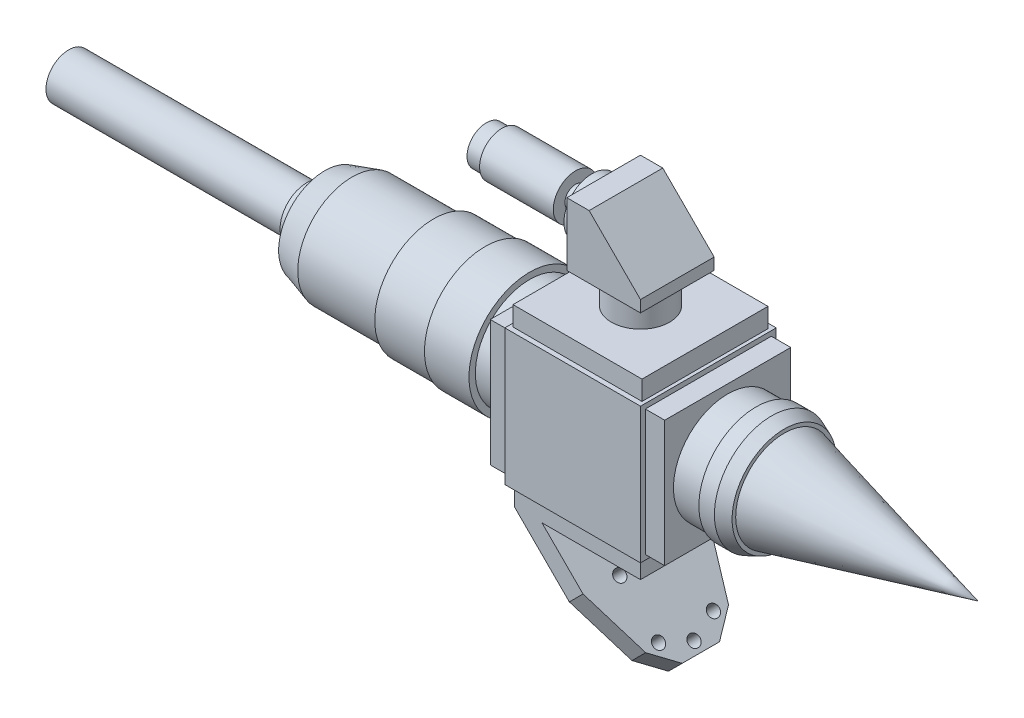
SolidWorks part; units mm, degrees
ref_plane "Front Plane" through (0, 0, 0) normal (0, 0, 1) x (1, 0, 0)
ref_plane "Top Plane" through (0, 0, 0) normal (0, 1, 0) x (1, 0, 0)
ref_plane "Right Plane" through (0, 0, 0) normal (1, 0, 0) x (0, 0, -1)
sketch "Sketch1" plane through (0, 0, 0) normal (0, 0, 1) x (1, 0, 0)
  line L1 (-35, 35) -> (35, 35) construction
  line L2 (-35, 35) -> (-35, -35) construction
  line L3 (-35, -35) -> (35, -35) construction
  line L4 (35, 35) -> (35, -35) construction
  dimension "D1" = 70
  dimension "D2" = 70
  dimension "D3" = 35
  dimension "D4" = 35
sketch "Sketch2" plane through (0, 0, 0) normal (0, 0, 1) x (1, 0, 0)
  line L0 (0, 0) -> (151.8037, 1.6334) construction
  line L1 (0, 0) -> (-331.3481, 0) construction
  line L3 (-35, 35) -> (35, 35)
  line L4 (-35, 35) -> (-35, -35)
  line L5 (-35, -35) -> (35, -35)
  line L6 (35, 35) -> (35, -35)
extrude "Boss-Extrude1" add sketch "Sketch2" along normal blind 35 and the other way blind 35
sketch "Sketch3" plane through (0, 0, 0) normal (0, 0, 1) x (1, 0, 0)
  line L0 (123.9014, 0) -> (-533.4709, 0) construction
  line L1 (35, 35) -> (35, -35) construction
  line L2 (35, -32.5) -> (45, -32.5)
  line L3 (35, -32.5) -> (35, 32.5)
  line L4 (-123.9014, 0) -> (533.4709, 0) construction
  line L5 (45, -32.5) -> (45, 32.5)
  line L6 (35, 32.5) -> (45, 32.5)
  line L7 (0, 0.6089) -> (0, 46.7598) construction
  dimension "D1" = 32.5
  dimension "D2" = 10
extrude "Boss-Extrude2" add sketch "Sketch3" along normal blind 32.5 and the other way blind 32.5
sketch "Sketch20" plane through (0, 0, 0) normal (0, 0, 1) x (1, 0, 0)
  line L0 (-35, 35) -> (-35, -35) construction
  line L1 (-35, 32.5) -> (-45, 32.5)
  line L2 (-35, 32.5) -> (-35, -32.5)
  line L3 (-35, -32.5) -> (-45, -32.5)
  line L4 (-45, 32.5) -> (-45, -32.5)
  line L5 (0, 0) -> (-92.839, 0) construction
  dimension "D1" = 10
  dimension "D2" = 32.5
  dimension "D3" = 65
extrude "Boss-Extrude10" add sketch "Sketch20" along normal blind 32.5 and the other way blind 32.5
sketch "Sketch4" plane through (0, 0, 0) normal (0, 0, 1) x (1, 0, 0)
  line L0 (126.079, 0) -> (-324.8833, 0) construction
  line L1 (45, 28) -> (59.608, 28)
  line L2 (45, -32.5) -> (45, 32.5) construction
  line L3 (59.608, 28) -> (59.608, 29.5)
  line L4 (59.608, 29.5) -> (67.608, 29.5)
  line L5 (67.608, 29.5) -> (74.108, 26.857)
  line L6 (74.108, 26.857) -> (74.108, 0)
  line L7 (45, 28) -> (45, 0)
  line L24 (74.108, 0) -> (45, 0)
  dimension "D1" = 28
  dimension "D2" = 1.5
  dimension "D3" = 8
  dimension "D4" = 6.5
revolve "Revolve1" add sketch "Sketch4" angle 360 about L0
sketch "Sketch5" plane through (0, 0, 0) normal (0, 0, 1) x (1, 0, 0)
  line L0 (0, 0) -> (243.065, 0) construction
  line L1 (74.108, 25) -> (174.108, 0)
  line L2 (74.108, -26.857) -> (74.108, 26.857) construction
  line L3 (174.108, 0) -> (74.108, 0)
  line L4 (74.108, 0) -> (74.108, 25)
  dimension "D1" = 100
  dimension "D2" = 25
revolve "Revolve2" add sketch "Sketch5" angle 360 about L0
sketch "Sketch11" plane through (0, 0, 0) normal (0, 0, 1) x (1, 0, 0)
  line L0 (0, 0) -> (-327.6417, 0) construction
  line L1 (-45, 28) -> (-57.2011, 28)
  line L2 (-57.2011, 28) -> (-57.2011, 31.2886)
  line L3 (-57.2011, 31.2886) -> (-80.1478, 31.2886)
  line L4 (-80.1478, 31.2886) -> (-80.1478, 30.3397)
  line L5 (-80.1478, 30.3397) -> (-106.7356, 30.3397)
  line L6 (-106.7356, 30.3397) -> (-106.7356, 28)
  line L7 (-106.7356, 28) -> (-148.8045, 28)
  line L8 (-148.8045, 28) -> (-162.9019, 23.7683)
  line L9 (-162.9019, 23.7683) -> (-162.9019, 13.7518)
  line L10 (-162.9019, 13.7518) -> (-172.1765, 13.7518)
  line L11 (-172.1765, 13.7518) -> (-172.1765, 11.7113)
  line L12 (-172.1765, 11.7113) -> (-294.986, 11.7113)
  line L13 (-294.986, 11.7113) -> (-294.986, 0)
  line L14 (-45, 28) -> (-45, 0)
  line L15 (-294.986, 0) -> (-45, 0)
revolve "Revolve4" add sketch "Sketch11" angle 360 about L0
sketch "Sketch10" [suppressed] plane through (0, 0, 0) normal (0, 0, 1) x (1, 0, 0)
  line L0 (0, 0) -> (0, 255.2777) construction
  line L1 (28, 35) -> (28, 47.2011)
  line L2 (28, 47.2011) -> (31.2886, 47.2011)
  line L3 (31.2886, 47.2011) -> (31.2886, 70.1478)
  line L4 (31.2886, 70.1478) -> (30.3397, 70.1478)
  line L5 (30.3397, 70.1478) -> (30.3397, 96.7356)
  line L6 (30.3397, 96.7356) -> (28, 96.7356)
  line L7 (28, 96.7356) -> (28, 138.8045)
  line L8 (28, 138.8045) -> (23.7683, 152.9019)
  line L9 (23.7683, 152.9019) -> (13.7518, 152.9019)
  line L10 (13.7518, 152.9019) -> (13.7518, 162.1765)
  line L11 (13.7518, 162.1765) -> (11.7113, 162.1765)
  line L12 (11.7113, 162.1765) -> (11.7113, 284.986)
  line L13 (11.7113, 284.986) -> (0, 284.986)
  line L14 (28, 35) -> (0, 35)
  line L15 (0, 284.986) -> (0, 35)
revolve "Revolve3" [suppressed] add sketch "Sketch10" angle 360 about L0
sketch "Sketch6" plane through (0, -35, 0) normal (0, -1, 0) x (1, 0, 0)
  line L12 (32.5, -32.5) -> (32.5, 32.5)
  line L13 (32.5, 32.5) -> (-32.5, 32.5)
  line L14 (-32.5, 32.5) -> (-32.5, -32.5)
  line L15 (-32.5, -32.5) -> (32.5, -32.5)
  line L16 (32.5, -32.5) -> (32.5, 32.5)
  line L17 (32.5, 32.5) -> (-32.5, 32.5)
  line L18 (-32.5, 32.5) -> (-32.5, -32.5)
  line L19 (-32.5, -32.5) -> (32.5, -32.5)
  dimension "D1" = 2.5
extrude "Boss-Extrude4" add sketch "Sketch6" along normal blind 10
sketch "Sketch7" plane through (0, -45, 0) normal (0, -1, 0) x (1, 0, 0)
  line L0 (-32.5, -32.5) -> (32.5, -32.5) construction
  line L1 (-32.5, 32.5) -> (-22.5, 32.5)
  line L2 (-32.5, 32.5) -> (-32.5, -32.5)
  line L3 (-32.5, -32.5) -> (-22.5, -32.5)
  line L4 (-22.5, 32.5) -> (-22.5, -32.5)
  dimension "D1" = 10
extrude "Boss-Extrude5" [suppressed] add sketch "Sketch7" along normal blind 80
sketch "Sketch8" [suppressed] plane through (-22.5, 0, 0) normal (1, 0, 0) x (0, 0, -1)
  circle A0 centre (14.1527, -85.773) radius 2.9667
  circle A1 centre (0, -80.1198) radius 3.1037
  circle A2 centre (-14.1565, -85.8978) radius 3.0437
  circle A3 centre (-14.2891, -114.259) radius 3.0277
  circle A4 centre (14.1527, -114.259) radius 3.1065
extrude "Cut-Extrude1" [suppressed] cut sketch "Sketch8" against normal through all
sketch "Sketch12" plane through (0, 0, 0) normal (0, 0, 1) x (1, 0, 0)
  line L0 (0, 0) -> (0, 177.9148) construction
  line L1 (-35, 35) -> (35, 35) construction
  line L2 (33.2718, 35) -> (-33.2718, 35)
  line L3 (33.2718, 35) -> (33.2718, 45)
  line L4 (33.2718, 45) -> (-33.2718, 45)
  line L6 (-33.2718, 35) -> (-33.2718, 45)
  dimension "D1" = 10
extrude "Boss-Extrude6" add sketch "Sketch12" along normal blind 32.5 and the other way blind 32.5
sketch "Sketch13" plane through (0, 0, 0) normal (0, 0, 1) x (1, 0, 0)
  line L0 (0, 0) -> (0, 100.1615) construction
  line L1 (33.2718, 45) -> (-33.2718, 45) construction
  line L2 (15, 45) -> (0, 45)
  line L3 (15, 45) -> (15, 60.8865)
  line L4 (15, 60.8865) -> (0, 60.8865)
  line L5 (0, 45) -> (0, 60.8865)
  dimension "D1" = 15
revolve "Revolve5" add sketch "Sketch13" angle 360 about L0
sketch "Sketch14" plane through (0, 0, 0) normal (0, 0, 1) x (1, 0, 0)
  line L0 (-82.1235, 76.9007) -> (21.0765, 76.9007) construction
  line L1 (-19, 60.6507) -> (19, 60.6507)
  line L2 (19, 60.6507) -> (19, 66.6507)
  line L3 (19, 66.6507) -> (-7.5, 93.1507)
  line L4 (-7.5, 93.1507) -> (-19, 93.1507)
  line L5 (-19, 93.1507) -> (-19, 60.6507)
  line L6 (0, 0) -> (0, 95.9156) construction
  dimension "D1" = 38
  dimension "D2" = 19
  dimension "D3" = 6
  dimension "D4" = 45
  dimension "D5" = 32.5
  dimension "D6" = 16.25
extrude "Boss-Extrude7" add sketch "Sketch14" along normal blind 19 and the other way blind 19
sketch "Sketch15" plane through (0, 0, 0) normal (0, 0, 1) x (1, 0, 0)
  line L0 (23.0816, 76.9007) -> (-92.3845, 76.9007) construction
  line L1 (-19, 60.6507) -> (19, 60.6507) construction
  line L2 (-19, 91.4007) -> (-25, 91.4007)
  line L3 (-25, 91.4007) -> (-25, 82.4007)
  line L4 (-25, 82.4007) -> (-33.5, 82.4007)
  line L5 (-33.5, 82.4007) -> (-33.5, 88.4007)
  line L6 (-33.5, 88.4007) -> (-71.5, 88.4007)
  line L7 (-71.5, 88.4007) -> (-71.5, 86.9007)
  line L8 (-71.5, 86.9007) -> (-79.5, 86.9007)
  line L9 (-79.5, 86.9007) -> (-79.5, 76.9007)
  line L10 (-79.5, 76.9007) -> (-19, 76.9007)
  line L11 (-19, 76.9007) -> (-19, 91.4007)
  line L12 (-19, 93.1507) -> (-19, 60.6507) construction
  dimension "D1" = 16.25
  dimension "D2" = 14.5
  dimension "D3" = 5.5
  dimension "D4" = 11.5
  dimension "D5" = 10
  dimension "D6" = 6
  dimension "D7" = 8.5
  dimension "D8" = 38
  dimension "D9" = 8
revolve "Revolve6" add sketch "Sketch15" angle 360 about L0
sketch "Sketch16" plane through (0, 0, 0) normal (0, 0, 1) x (1, 0, 0)
  line L0 (0, 0) -> (-98.4067, 0) construction
  line L2 (-45, 15) -> (-60.65, 15)
  line L3 (-45, 15) -> (-45, 0)
  line L4 (-45, 0) -> (-60.65, 0)
  line L5 (-60.65, 15) -> (-60.65, 0)
  dimension "D1" = 15.65
  dimension "D2" = 15
revolve "Revolve7" add sketch "Sketch16" angle 360 about L0
sketch "Sketch17" [suppressed] plane through (0, 0, 0) normal (0, 0, 1) x (1, 0, 0)
  line L0 (0, 0) -> (-124.0041, 0) construction
  line L1 (-60.65, -20.92) -> (-60.65, 19)
  line L2 (-60.65, 19) -> (-93.15, 19)
  line L3 (-93.15, 19) -> (-93.15, 5.58)
  line L4 (-93.15, 5.58) -> (-66.65, -20.92)
  line L5 (-66.65, -20.92) -> (-60.65, -20.92)
  dimension "D1" = 6
  dimension "D2" = 32.5
  dimension "D3" = 13.42
  dimension "D4" = 19
  dimension "D5" = 45
  dimension "D6" = 39.92
extrude "Boss-Extrude8" [suppressed] add sketch "Sketch17" along normal blind 19 and the other way blind 19
sketch "Sketch18" [suppressed] plane through (0, 0, 0) normal (0, 0, 1) x (1, 0, 0)
  line L0 (-76.9, -14.8998) -> (-76.9, 53.5448) construction
  line L1 (-60.65, -20.92) -> (-60.65, 19) construction
  line L2 (-62.4, 18.9356) -> (-62.4, 24.9356)
  line L3 (-62.4, 24.9356) -> (-71.4, 24.9356)
  line L4 (-71.4, 24.9356) -> (-71.4, 33.4356)
  line L5 (-71.4, 33.4356) -> (-65.4, 33.4356)
  line L6 (-65.4, 33.4356) -> (-65.4, 71.4356)
  line L7 (-65.4, 71.4356) -> (-66.9, 71.4356)
  line L8 (-66.9, 71.4356) -> (-66.9, 79.4356)
  line L9 (-66.9, 79.4356) -> (-76.9, 79.4356)
  line L10 (-76.9, 79.4356) -> (-76.9, 18.9356)
  line L11 (-76.9, 18.9356) -> (-62.4, 18.9356)
  dimension "D1" = 16.25
  dimension "D2" = 6
  dimension "D3" = 8.5
  dimension "D4" = 38
  dimension "D5" = 8
revolve "Revolve8" [suppressed] add sketch "Sketch18" angle 360 about L0
sketch "Sketch21" [suppressed] plane through (-45, 0, 0) normal (-1, 0, 0) x (0, 0, 1)
  line L0 (0, 0) -> (55.7472, 0) construction
  line L1 (0, 0) -> (0, 37.1138) construction
  line L2 (27.5, 29.558) -> (27.5, 20.8768) construction
  line L3 (22.9517, 27.5) -> (31.1506, 27.5) construction
  line L5 (32.5, 32.5) -> (20.0462, 32.5)
  line L6 (32.5, 32.5) -> (32.5, 0)
  line L7 (32.5, 0) -> (20.0462, 0)
  line L8 (20.0462, 32.5) -> (20.0462, 0)
  circle A0 centre (27.5, 27.5) radius 3
  dimension "D1" = 27.5
  dimension "D2" = 27.5
extrude "Boss-Extrude11" [suppressed] add sketch "Sketch21" along normal blind 3
sketch "Sketch22" [suppressed] plane through (-45, 0, 0) normal (-1, 0, 0) x (0, 0, 1)
  line L1 (20.0462, 32.5) -> (23.0462, 32.5)
  line L2 (20.0462, 32.5) -> (20.0462, 0)
  line L3 (20.0462, 0) -> (23.0462, 0)
  line L4 (23.0462, 32.5) -> (23.0462, 0)
  dimension "D1" = 3
extrude "Boss-Extrude12" [suppressed] add sketch "Sketch22" along normal blind 50
mirror "Mirror1" [suppressed]
mirror "Mirror5" [suppressed] about plane through (0, 0, 0) normal (0, 0, 1)
mirror "Mirror6" [suppressed]
sketch "Sketch23" [suppressed] plane through (-95, 0, 0) normal (-1, 0, 0) x (0, 0, 1)
  line L1 (-32.5, 32.5) -> (32.5, 32.5)
  line L2 (-32.5, 32.5) -> (-32.5, -32.5)
  line L3 (-32.5, -32.5) -> (32.5, -32.5)
  line L4 (32.5, 32.5) -> (32.5, -32.5)
  circle A0 centre (27.5, 27.5) radius 3 construction
  circle A1 centre (27.5, 27.5) radius 3
  circle A2 centre (27.5, -27.5) radius 3 construction
  circle A3 centre (-27.5, -27.5) radius 3 construction
  circle A4 centre (-27.5, 27.5) radius 3 construction
  circle A5 centre (27.5, -27.5) radius 3
  circle A6 centre (-27.5, -27.5) radius 3
  circle A7 centre (-27.5, 27.5) radius 3
extrude "Boss-Extrude13" [suppressed] add sketch "Sketch23" along normal blind 3
sketch "Sketch24" plane through (0, 0, 32.5) normal (0, 0, 1) x (1, 0, 0)
  line L0 (-32.5, -45) -> (24.0685, -101.5685)
  line L2 (31.1396, -94.4975) -> (-18.3579, -45)
  line L3 (32.5, -45) -> (-32.5, -45) construction
  line L4 (-18.3579, -45) -> (-32.5, -45)
  line L5 (24.0685, -101.5685) -> (31.1396, -94.4975)
  dimension "D1" = 10
  dimension "D2" = 45
  dimension "D3" = 80
extrude "Boss-Extrude14" add sketch "Sketch24" against normal up to surface (65 mm away) up to face at (0, -40, -32.5)
sketch "Sketch25" plane through (-38.75, -38.75, 0) normal (-0.7071, -0.7071, 0) x (0, 0, 1)
  line L0 (0, -88.8388) -> (0, -8.8388) construction
  line L1 (-32.5, -88.8388) -> (32.5, -88.8388) construction
  line L2 (32.5, -8.8388) -> (-32.5, -8.8388) construction
  line L3 (2.1962, -86.035) -> (-2.1962, -81.6427) construction
  line L4 (-13.3383, -80.981) -> (-14.946, -74.981) construction
  line L5 (-11.946, -51.8929) -> (-16.3383, -47.5005) construction
  circle A0 centre (0, -83.8388) radius 3.0012
  circle A1 centre (0, -63.8388) radius 20 construction
  circle A2 centre (-14.1421, -49.6967) radius 3
  circle A3 centre (-14.1421, -77.981) radius 3
  circle A4 centre (14.1421, -49.6967) radius 3
  circle A5 centre (14.1421, -77.981) radius 3
extrude "Cut-Extrude2" cut sketch "Sketch25" against normal up to next
sketch "Sketch26" plane through (-38.75, -38.75, 0) normal (-0.7071, -0.7071, 0) x (0, 0, 1)
  line L0 (0, -88.8388) -> (0, -8.8388) construction
  line L1 (-32.5, -88.8388) -> (32.5, -88.8388) construction
  line L2 (32.5, -8.8388) -> (-32.5, -8.8388) construction
  line L3 (-32.5, -48.8388) -> (-21.3703, -78.8051)
  line L4 (-32.5, -88.8388) -> (-32.5, -8.8388) construction
  line L5 (-21.3703, -78.8051) -> (-9.6273, -88.8388)
  line L6 (-9.6273, -88.8388) -> (-32.5, -88.8388)
  line L7 (-32.5, -88.8388) -> (-32.5, -48.8388)
  line L8 (32.5, -48.8388) -> (21.3703, -78.8051)
  line L9 (32.5, -88.8388) -> (32.5, -48.8388)
  line L10 (9.6273, -88.8388) -> (32.5, -88.8388)
  line L11 (21.3703, -78.8051) -> (9.6273, -88.8388)
extrude "Cut-Extrude3" cut sketch "Sketch26" against normal up to next
